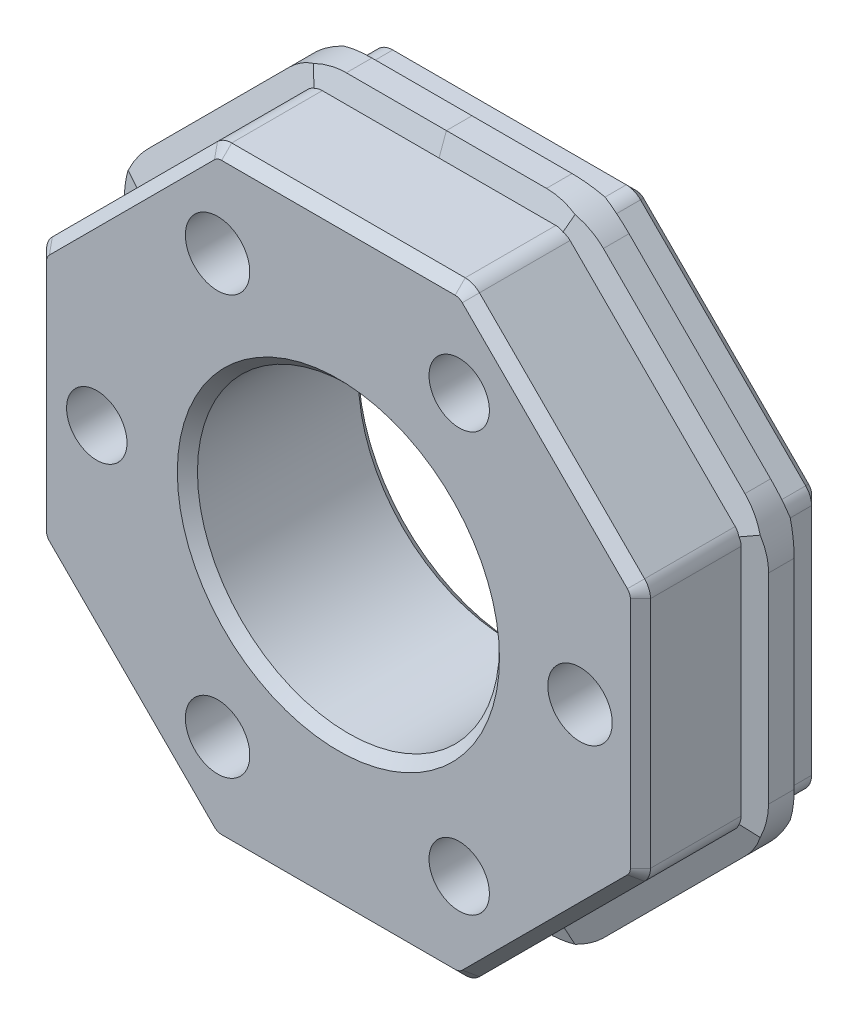
SolidWorks part; units mm, degrees
material "6061 合金"
ref_plane "前视基准面" through (0, 0, 0) normal (0, 0, 1) x (1, 0, 0)
ref_plane "上视基准面" through (0, 0, 0) normal (0, 1, 0) x (1, 0, 0)
ref_plane "右视基准面" through (0, 0, 0) normal (1, 0, 0) x (0, 0, -1)
other "Configuration Table"
sketch "草图1" plane through (0, 0, 0) normal (0, 0, 1) x (1, 0, 0)
  line L1 (-16, 16) -> (16, 16)
  line L2 (-16, 16) -> (-16, -16)
  line L3 (-16, -16) -> (16, -16)
  line L4 (16, 16) -> (16, -16)
  line L5 (0, -16) -> (0, 16) construction
  line L6 (-16, 0) -> (16, 0) construction
  circle A0 centre (0, 0) radius 7.5
  circle A1 centre (0, 0) radius 18 construction
  circle A2 centre (0, 0) radius 12 construction
  dimension "D1" = 36
  dimension "D2" = 15
  dimension "D3" = 24
  dimension "D6" = 32
  dimension "D7" = 32
extrude "凸台-拉伸1" add sketch "草图1" along normal mid plane 6
sketch "草图23" plane through (0, 0, 3) normal (0, 0, 1) x (1, 0, 0)
  line L0 (16, 16) -> (16, -16)
  line L8 (-16, -16) -> (16, -16)
  line L11 (16, -16) -> (16, 16)
  line L12 (16, -16) -> (16, 16)
  line L14 (16, 16) -> (-16, 16)
  line L15 (-16, 16) -> (-16, -16)
  line L16 (-16, -16) -> (16, -16)
  line L22 (16, 16) -> (-16, 16)
  line L23 (-16, 16) -> (-16, -16)
  line M23 (-16, -16) -> (16, -16)
  line M25 (16, -16) -> (16, 16)
  line M35 (16, 16) -> (-16, 16)
  line M37 (-16, 16) -> (-16, -16)
  circle M39 centre (0, 0) radius 7.5
  dimension "D1" = 0
extrude "凸台-拉伸4" add sketch "草图23" along normal blind 3 contours M23 M25 M35 M37 M39 region at (15.5475, 0, 3)
sketch "草图8" plane through (0, 0, -3) normal (0, 0, -1) x (-1, 0, 0)
  circle A0 centre (0, 0) radius 12 construction
  point P0 (-12, 0)
  point P1 (6, 10.3923)
  point P9 (6, -10.3923)
  dimension "D1" = 24
  dimension "D2" = 3
hole_wizard "M3 六角圆柱头螺钉的柱形沉头孔1" positions "草图8" profile "草图9" counterbore size "M3" standard "GB" end condition through all
sketch "草图9" plane through (12, 0, -3) normal (1, 0, 0) x (0, 1, 0)
  line L0 (0, 0) -> (0, 9)
  line L1 (0, 9) -> (1.6, 9)
  line L3 (1.6, 9) -> (1.6, 5)
  line L4 (1.6, 5) -> (2.85, 5)
  line L5 (2.85, 5) -> (2.85, 0)
  line L7 (2.85, 0) -> (0, 0)
  line L11 (0, -6.35) -> (0, 107.95) construction
  dimension "通孔孔直径" = 3.2
  dimension "通孔孔深度" = 9
  dimension "柱形沉头孔直径" = 5.7
  dimension "柱形沉头孔深度" = 5
hole_wizard "Ø3.0mm 暗销孔1" positions "草图24" profile "草图25" hole size "Ø3.0" standard "BSI"
sketch "草图24" plane through (0, 0, 6) normal (0, 0, 1) x (1, 0, 0)
  circle A0 centre (0, 0) radius 12 construction
  point P0 (-12, 0)
  point P13 (6, 10.3923)
  point P14 (6, -10.3923)
  dimension "D1" = 24
  dimension "D2" = 3
sketch "草图25" plane through (-12, 0, 6) normal (1, 0, 0) x (0, -1, 0)
  line L0 (0, 0) -> (0, 4.9013)
  line L1 (0, 4.9013) -> (1.5, 4)
  line L2 (1.5, 4) -> (1.5, 0)
  line L5 (1.5, 0) -> (0, 0)
  line L10 (0, 4.9013) -> (-1.5, 4) construction
  line L11 (0, -6.35) -> (0, 107.95) construction
  dimension "孔直径" = 3
  dimension "孔深度" = 4
  dimension "导头角度" = 118
ref_plane "基准面1" through (0, 0, 0) normal (0, 0, -1) x (-1, 0, 0)
sketch "草图26" plane through (0, 0, -3) normal (0, 0, -1) x (-1, 0, 0)
  circle A0 centre (0, 0) radius 15
  dimension "D1" = 30
extrude "切除-拉伸1" cut sketch "草图26" against normal through all flip side to cut
sketch "草图35" plane through (0, 0, 6) normal (0, 0, 1) x (1, 0, 0)
  line L0 (-18.5745, 0) -> (16.9837, 0) construction
ref_plane "基准面2" through (0, 0, 0) normal (0, -1, 0) x (1, 0, 0)
sketch "草图42" plane through (0, 0, -3) normal (0, 0, -1) x (-1, 0, 0)
  line L1 (-6.2132, 15) -> (-15, 6.2132)
  line L2 (-15, 6.2132) -> (-15, -6.2132)
  line L3 (-15, -6.2132) -> (-6.2132, -15)
  line L4 (-6.2132, -15) -> (6.2132, -15)
  line L5 (6.2132, -15) -> (15, -6.2132)
  line L6 (15, -6.2132) -> (15, 6.2132)
  line L7 (15, 6.2132) -> (6.2132, 15)
  line L8 (6.2132, 15) -> (-6.2132, 15)
  circle A0 centre (0, 0) radius 15 construction
  circle A1 centre (0, 0) radius 15 construction
  circle A2 centre (0, 0) radius 15
extrude "凸台-拉伸5" add sketch "草图42" against normal up to surface (9 mm away) contours A2 L8 L1 | A2 L7 L8 | A2 L6 L7 | A2 L5 L6 | A2 L4 L5 | A2 L3 L4 | A2 L2 L3 | A2 L1 L2 region at (5.8394, 14.0975, -3) region at (14.0975, 5.8394, -3) region at (-5.8394, 14.0975, -3) region at (14.0975, -5.8394, -3) region at (-14.0975, 5.8394, -3) region at (5.8394, -14.0975, -3) region at (-14.0975, -5.8394, -3) region at (-5.8394, -14.0975, -3) up to face at (7.5, 0, 6)
sketch "草图43" plane through (0, 0, 0) normal (1, 0, 0) x (0, 0, -1)
  line L1 (-1, 15) -> (1, 15)
  line L2 (-6, 15) -> (3, 15) construction
  line L3 (1, 15) -> (0.636, 16)
  line L4 (0.636, 16) -> (-0.636, 16)
  line L5 (-0.636, 16) -> (-1, 15)
  line L8 (3, 6.2132) -> (3, 15) construction
  line L9 (0, 22.7244) -> (0, -9.6288) construction
  dimension "D2" = 40
  dimension "D3" = 1
  dimension "D4" = 2
ref_plane "基准面3" through (0, 0, -1) normal (0, 0, -1) x (-1, 0, 0)
sketch "草图44" plane through (0, 0, -1) normal (0, 0, -1) x (-1, 0, 0)
  line L8 (-6.2132, 15) -> (-15, 6.2132)
  line L9 (-15, 6.2132) -> (-15, -6.2132)
  line L10 (-15, -6.2132) -> (-6.2132, -15)
  line L11 (-6.2132, -15) -> (6.2132, -15)
  line L12 (6.2132, -15) -> (15, -6.2132)
  line L13 (15, -6.2132) -> (15, 6.2132)
  line L14 (15, 6.2132) -> (6.2132, 15)
  line L15 (6.2132, 15) -> (-6.2132, 15)
  line L16 (-6.2132, 15) -> (-15, 6.2132)
  line L17 (-15, 6.2132) -> (-15, -6.2132)
  line L18 (-15, -6.2132) -> (-6.2132, -15)
  line L19 (-6.2132, -15) -> (6.2132, -15)
  line L20 (6.2132, -15) -> (15, -6.2132)
  line L21 (15, -6.2132) -> (15, 6.2132)
  line L22 (15, 6.2132) -> (6.2132, 15)
  line L23 (6.2132, 15) -> (-6.2132, 15)
  dimension "D1" = 0
sweep "扫描1" add profiles "草图43" path "草图44"
fillet "圆角1" radius 1 16 edges at (15, 6.2132, 3.5) (15, -6.2132, 3.5) (6.2132, -15, 3.5) (-6.2132, -15, 3.5) (-15, -6.2132, 3.5) (-15, 6.2132, 3.5) (6.2132, 15, 3.5) (-6.2132, 15, 3.5) (6.2132, 15, -2) (15, 6.2132, -2) (15, -6.2132, -2) (6.2132, -15, -2) (-6.2132, -15, -2) (-15, -6.2132, -2) (-15, 6.2132, -2) (-6.2132, 15, -2)
chamfer "倒角1" distance 0.5 angle 45 34 edges at (0, -15, -3) (-6.1817, -14.9239, -3) (6.1817, -14.9239, -3) (-10.6066, -10.6066, -3) (10.6066, -10.6066, -3) (-14.9239, -6.1817, -3) (14.9239, -6.1817, -3) (-15, 0, -3) (15, 0, -3) (-14.9239, 6.1817, -3) (14.9239, 6.1817, -3) (-10.6066, 10.6066, -3) (10.6066, 10.6066, -3) (-6.1817, 14.9239, -3) (6.1817, 14.9239, -3) (0, 15, -3) (0, -15, 6) (-6.1817, -14.9239, 6) (6.1817, -14.9239, 6) (-10.6066, -10.6066, 6) (10.6066, -10.6066, 6) (-14.9239, -6.1817, 6) (14.9239, -6.1817, 6) (-15, 0, 6) (15, 0, 6) (-14.9239, 6.1817, 6) (14.9239, 6.1817, 6) (-10.6066, 10.6066, 6) (10.6066, 10.6066, 6) (-6.1817, 14.9239, 6) (6.1817, 14.9239, 6) (0, 15, 6) (7.5, 0, 6) (7.5, 0, -3)
fillet "圆角2" radius 4 8 edges at (6.6274, 16, 0) (-6.6274, 16, 0) (-16, 6.6274, 0) (-16, -6.6274, 0) (-6.6274, -16, 0) (6.6274, -16, 0) (16, -6.6274, 0) (16, 6.6274, 0)
